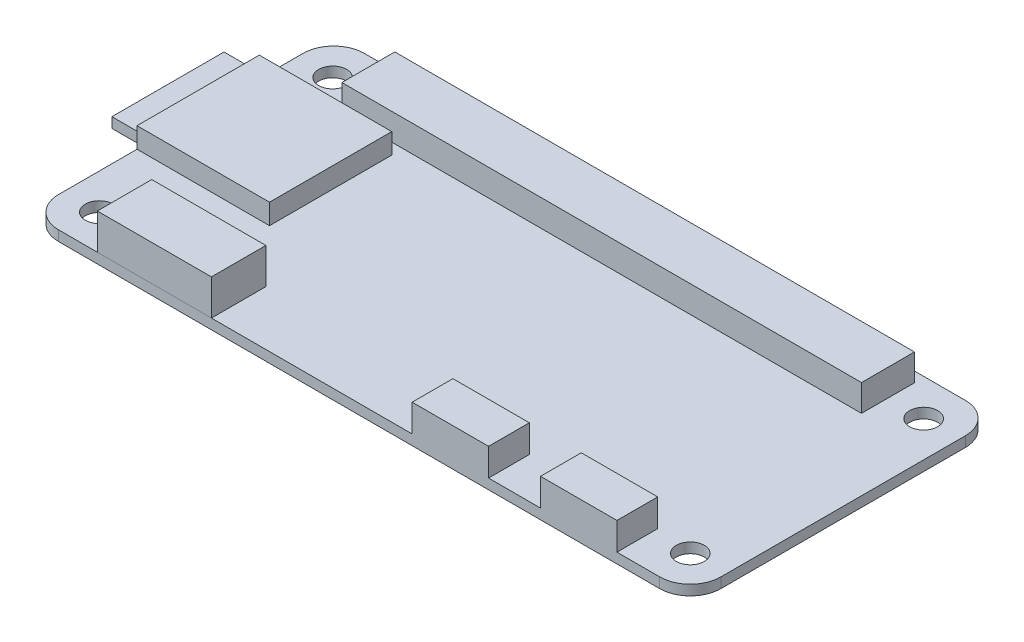
SolidWorks part; units mm, degrees
ref_plane "前视基准面" through (0, 0, 0) normal (0, 0, 1) x (1, 0, 0)
ref_plane "上视基准面" through (0, 0, 0) normal (0, 1, 0) x (1, 0, 0)
ref_plane "右视基准面" through (0, 0, 0) normal (1, 0, 0) x (0, 0, -1)
sketch "zero" plane through (0, 0, 0) normal (0, 1, 0) x (1, 0, 0)
  line L1 (-29.5, 15) -> (29.5, 15)
  line L2 (-32.5, 12) -> (-32.5, -12)
  line L3 (-29.5, -15) -> (29.5, -15)
  line L4 (32.5, 12) -> (32.5, -12)
  line L5 (-32.5, 15) -> (32.5, -15) construction
  line L6 (-32.5, -15) -> (32.5, 15) construction
  line L7 (-25.7, -15) -> (-14.5, -15)
  line L8 (-25.7, -15) -> (-25.7, -9.6569)
  line L9 (-25.7, -9.6569) -> (-14.5, -9.6569)
  line L10 (-14.5, -15) -> (-14.5, -9.6569)
  line L11 (5.2, -15) -> (12.7, -15)
  line L12 (5.2, -15) -> (5.2, -11)
  line L13 (5.2, -11) -> (12.7, -11)
  line L14 (12.7, -15) -> (12.7, -11)
  line L15 (17.8, -15) -> (25.3, -15)
  line L16 (17.8, -15) -> (17.8, -11)
  line L17 (17.8, -11) -> (25.3, -11)
  line L18 (25.3, -15) -> (25.3, -11)
  line L19 (-32.5, 7.7) -> (-19.5, 7.7)
  line L20 (-32.5, 7.7) -> (-32.5, -4.3)
  line L21 (-32.5, -4.3) -> (-19.5, -4.3)
  line L22 (-19.5, 7.7) -> (-19.5, -4.3)
  line L23 (-25.5, 14) -> (25.5, 14)
  line L24 (-25.5, 14) -> (-25.5, 8.8)
  line L25 (-25.5, 8.8) -> (25.5, 8.8)
  line L26 (25.5, 14) -> (25.5, 8.8)
  line L27 (-19.5, 7.2329) -> (-35.5, 7.2329)
  line L28 (-19.5, 7.2329) -> (-19.5, -3.7671)
  line L29 (-19.5, -3.7671) -> (-35.5, -3.7671)
  line L30 (-35.5, 7.2329) -> (-35.5, -3.7671)
  arc A0 (29.5, -15) -> (32.5, -12) centre (29.5, -12) ccw
  arc A1 (29.5, 15) -> (32.5, 12) centre (29.5, 12) cw
  arc A2 (-32.5, -12) -> (-29.5, -15) centre (-29.5, -12) ccw
  arc A3 (-29.5, 15) -> (-32.5, 12) centre (-29.5, 12) ccw
  circle A4 centre (-29, 11.4) radius 3
  circle A5 centre (-29, -11.5) radius 3
  circle A6 centre (29, 11.4) radius 3
  circle A7 centre (29, -11.5) radius 3
  circle A8 centre (-29, 11.4) radius 1.375
  circle A9 centre (-29, -11.5) radius 1.375
  circle A10 centre (29, -11.5) radius 1.375
  circle A11 centre (29, 11.4) radius 1.375
  point P0 (0, 0)
  dimension "D3" = 3
  dimension "D4" = 6
  dimension "D9" = 2.75
  dimension "D1" = 65
  dimension "D2" = 30
  dimension "D5" = 3.6
  dimension "D6" = 3.5
  dimension "D7" = 3.5
  dimension "D8" = 3.5
  dimension "D10" = 12
  dimension "D11" = 7.3
  dimension "D12" = 13
  dimension "D13" = 11.2
  dimension "D14" = 6.8
  dimension "D15" = 19.7
  dimension "D16" = 7.5
  dimension "D17" = 7.5
  dimension "D18" = 5.1
  dimension "D19" = 4
  dimension "D20" = 5.2
  dimension "D21" = 7
  dimension "D22" = 7
  dimension "D23" = 1
  dimension "D24" = 11
  dimension "D25" = 16
sketch "sugar" plane through (0, 0, 0) normal (0, 1, 0) x (1, 0, 0)
  line L1 (-29.5, 15) -> (29.5, 15)
  line L2 (-32.5, 12) -> (-32.5, -12)
  line L3 (-29.5, -15) -> (29.5, -15)
  line L4 (32.5, 12) -> (32.5, -12)
  line L5 (-32.5, 15) -> (32.5, -15) construction
  line L6 (-32.5, -15) -> (32.5, 15) construction
  line L7 (23.5, -11.5) -> (19.5, -11.5)
  line L8 (23.5, -11.5) -> (23.5, -13.9082)
  line L9 (23.5, -13.9082) -> (19.5, -13.9082)
  line L10 (19.5, -11.5) -> (19.5, -13.9082)
  line L11 (16, -11.0071) -> (8.5, -11.0071)
  line L12 (16, -11.0071) -> (16, -15)
  line L13 (16, -15) -> (8.5, -15)
  line L14 (8.5, -11.0071) -> (8.5, -15)
  line L15 (20.5, -13.9082) -> (22.5, -13.9082)
  line L16 (20.5, -13.9082) -> (20.5, -14.8173)
  line L17 (20.5, -14.8173) -> (22.5, -14.8173)
  line L18 (22.5, -13.9082) -> (22.5, -14.8173)
  arc A0 (29.5, 15) -> (32.5, 12) centre (29.5, 12) cw
  arc A1 (29.5, -15) -> (32.5, -12) centre (29.5, -12) ccw
  arc A2 (-32.5, -12) -> (-29.5, -15) centre (-29.5, -12) ccw
  arc A3 (-29.5, 15) -> (-32.5, 12) centre (-29.5, 12) ccw
  circle A4 centre (-29, 11.4) radius 3
  circle A5 centre (-29, 11.4) radius 1.375
  circle A6 centre (-29, -11.5) radius 3
  circle A7 centre (-29, -11.5) radius 1.375
  circle A8 centre (29, 11.4) radius 3
  circle A9 centre (29, 11.4) radius 1.375
  circle A10 centre (29, -11.5) radius 3
  circle A11 centre (29, -11.5) radius 1.375
  dimension "D3" = 3
  dimension "D1" = 65
  dimension "D2" = 30
  dimension "D4" = 9
  dimension "D5" = 4
  dimension "D6" = 3.5
  dimension "D7" = 7.5
  dimension "D8" = 2
  dimension "D9" = 1
sketch "草图1" plane through (0, 0, 0) normal (0, 1, 0) x (1, 0, 0)
  line L4 (-32.5, 12) -> (-32.5, -12)
  line L5 (-29.5, -15) -> (29.5, -15)
  line L6 (32.5, -12) -> (32.5, 12)
  line L7 (29.5, 15) -> (-29.5, 15)
  line L8 (-32.5, 12) -> (-32.5, -12)
  line L9 (-29.5, -15) -> (29.5, -15)
  line L10 (32.5, -12) -> (32.5, 12)
  line L11 (29.5, 15) -> (-29.5, 15)
  circle A1 centre (29, 11.4) radius 1.375
  circle A2 centre (29, 11.4) radius 1.375
  circle A3 centre (29, -11.5) radius 1.375
  circle A4 centre (29, -11.5) radius 1.375
  circle A5 centre (-29, -11.5) radius 1.375
  circle A6 centre (-29, -11.5) radius 1.375
  circle A7 centre (-29, 11.4) radius 1.375
  circle A8 centre (-29, 11.4) radius 1.375
  arc A20 (-32.5, -12) -> (-29.5, -15) centre (-29.5, -12) ccw
  arc A21 (29.5, -15) -> (32.5, -12) centre (29.5, -12) ccw
  arc A22 (32.5, 12) -> (29.5, 15) centre (29.5, 12) ccw
  arc A23 (-29.5, 15) -> (-32.5, 12) centre (-29.5, 12) ccw
  arc A24 (-32.5, -12) -> (-29.5, -15) centre (-29.5, -12) ccw
  arc A25 (29.5, -15) -> (32.5, -12) centre (29.5, -12) ccw
  arc A26 (32.5, 12) -> (29.5, 15) centre (29.5, 12) ccw
  arc A27 (-29.5, 15) -> (-32.5, 12) centre (-29.5, 12) ccw
  dimension "D1" = 0
  dimension "D2" = 0
  dimension "D3" = 0
  dimension "D4" = 0
  dimension "D9" = 0
extrude "凸台-拉伸1" add sketch "草图1" along normal blind 1
ref_plane "基准面1" through (0, 1, 0) normal (0, 1, 0) x (1, 0, 0)
sketch "草图2" plane through (0, 1, 0) normal (0, 1, 0) x (1, 0, 0)
  line L20 (17.8, -15) -> (25.3, -15)
  line L21 (25.3, -15) -> (25.3, -11)
  line L22 (25.3, -11) -> (17.8, -11)
  line L23 (17.8, -11) -> (17.8, -15)
  line L24 (17.8, -15) -> (25.3, -15)
  line L25 (25.3, -15) -> (25.3, -11)
  line L26 (25.3, -11) -> (17.8, -11)
  line L27 (17.8, -11) -> (17.8, -15)
  line L28 (5.2, -15) -> (12.7, -15)
  line L29 (12.7, -15) -> (12.7, -11)
  line L30 (12.7, -11) -> (5.2, -11)
  line L31 (5.2, -11) -> (5.2, -15)
  line L32 (5.2, -15) -> (12.7, -15)
  line L33 (12.7, -15) -> (12.7, -11)
  line L34 (12.7, -11) -> (5.2, -11)
  line L35 (5.2, -11) -> (5.2, -15)
  dimension "D11" = 0
  dimension "D12" = 0
extrude "凸台-拉伸2" add sketch "草图2" along normal blind 2.7
sketch "草图3" plane through (0, 1, 0) normal (0, 1, 0) x (1, 0, 0)
  line L36 (-25.7, -15) -> (-14.5, -15)
  line L37 (-25.7, -9.6569) -> (-25.7, -15)
  line L38 (-14.5, -9.6569) -> (-25.7, -9.6569)
  line L39 (-14.5, -15) -> (-14.5, -9.6569)
  line L40 (-25.7, -15) -> (-14.5, -15)
  line L41 (-25.7, -9.6569) -> (-25.7, -15)
  line L42 (-14.5, -9.6569) -> (-25.7, -9.6569)
  line L43 (-14.5, -15) -> (-14.5, -9.6569)
  dimension "D13" = 0
extrude "凸台-拉伸3" add sketch "草图3" along normal blind 3.5 separate body
sketch "草图4" plane through (0, 1, 0) normal (0, 1, 0) x (1, 0, 0)
  line L12 (-19.5, 7.7) -> (-32.5, 7.7)
  line L13 (-19.5, -4.3) -> (-19.5, 7.7)
  line L14 (-32.5, -4.3) -> (-19.5, -4.3)
  line L15 (-32.5, 7.7) -> (-32.5, -4.3)
  line L16 (-19.5, 7.7) -> (-32.5, 7.7)
  line L17 (-19.5, -4.3) -> (-19.5, 7.7)
  line L18 (-32.5, -4.3) -> (-19.5, -4.3)
  line L19 (-32.5, 7.7) -> (-32.5, -4.3)
  dimension "D10" = 0
extrude "凸台-拉伸4" add sketch "草图4" along normal blind 2 separate body
sketch "草图5" plane through (0, 1, 0) normal (0, 1, 0) x (1, 0, 0)
  line L44 (-19.5, 7.2329) -> (-35.5, 7.2329)
  line L45 (-35.5, 7.2329) -> (-35.5, -3.7671)
  line L46 (-35.5, -3.7671) -> (-19.5, -3.7671)
  line L47 (-19.5, -3.7671) -> (-19.5, 7.2329)
  line L48 (-19.5, 7.2329) -> (-35.5, 7.2329)
  line L49 (-35.5, 7.2329) -> (-35.5, -3.7671)
  line L50 (-35.5, -3.7671) -> (-19.5, -3.7671)
  line L51 (-19.5, -3.7671) -> (-19.5, 7.2329)
  dimension "D14" = 0
extrude "凸台-拉伸5" add sketch "草图5" along normal blind 1
sketch "草图6" plane through (0, 1, 0) normal (0, 1, 0) x (1, 0, 0)
  line L0 (25.5, 14) -> (25.5, 8.8) construction
  line L1 (-25.5, 14) -> (25.5, 14) construction
  line L2 (-25.5, 8.8) -> (25.5, 8.8) construction
  line L3 (-25.5, 14) -> (-25.5, 8.8) construction
  line L4 (25.5, 14) -> (25.5, 8.8)
  line L5 (-25.5, 14) -> (25.5, 14)
  line L6 (-25.5, 8.8) -> (25.5, 8.8)
  line L7 (-25.5, 14) -> (-25.5, 8.8)
extrude "凸台-拉伸6" add sketch "草图6" along normal blind 2.62
